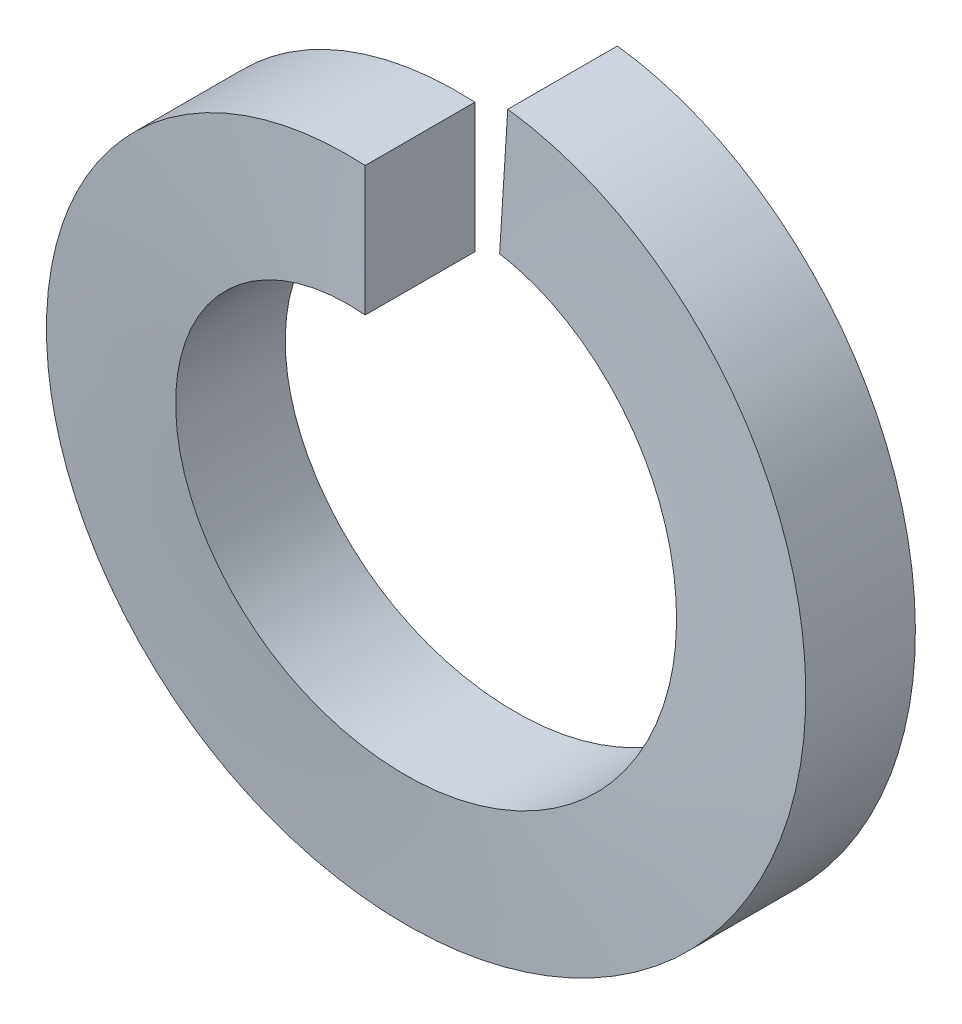
SolidWorks part; units mm, degrees
material "Stainless Steel 316"
ref_plane "Front Plane" through (0, 0, 0) normal (0, 0, 1) x (1, 0, 0)
ref_plane "Top Plane" through (0, 0, 0) normal (0, 1, 0) x (1, 0, 0)
ref_plane "Right Plane" through (0, 0, 0) normal (1, 0, 0) x (0, 0, -1)
sketch "Sketch1" plane through (0, 0, 0) normal (0, 0, 1) x (1, 0, 0)
  line L0 (0, 3.5) -> (0, 2.2) construction
  circle A0 centre (0, 0) radius 3.5
  circle A1 centre (0, 0) radius 2.2 construction
  dimension "ID" = 4.4
  dimension "OD" = 7
curve "Helix/Spiral1" pitch 1.2222 height 1.21 radius 3.5 left hand yes centre (0, 0, 0) axis (0, 0, -1) start towards (0, 1, 0) parameters "HT"=1.21
sketch "Sketch2" plane through (0, 0, 0) normal (1, 0, 0) x (0, 0, -1)
  line L1 (0, 3.5) -> (-1.1, 3.5)
  line L2 (0, 3.5) -> (0, 2.2)
  line L3 (0, 2.2) -> (-1.1, 2.2)
  line L4 (-1.1, 3.5) -> (-1.1, 2.2)
  dimension "THK" = 1.1
sweep "Sweep1" add profiles "Sketch2" path "Helix/Spiral1"
ref_axis "Axis1" through (0, 0, 1.2211) along (0, 0, -1)
equation "\"HT@Helix/Spiral1\" = \"THK@Sketch2\"*1.1"
